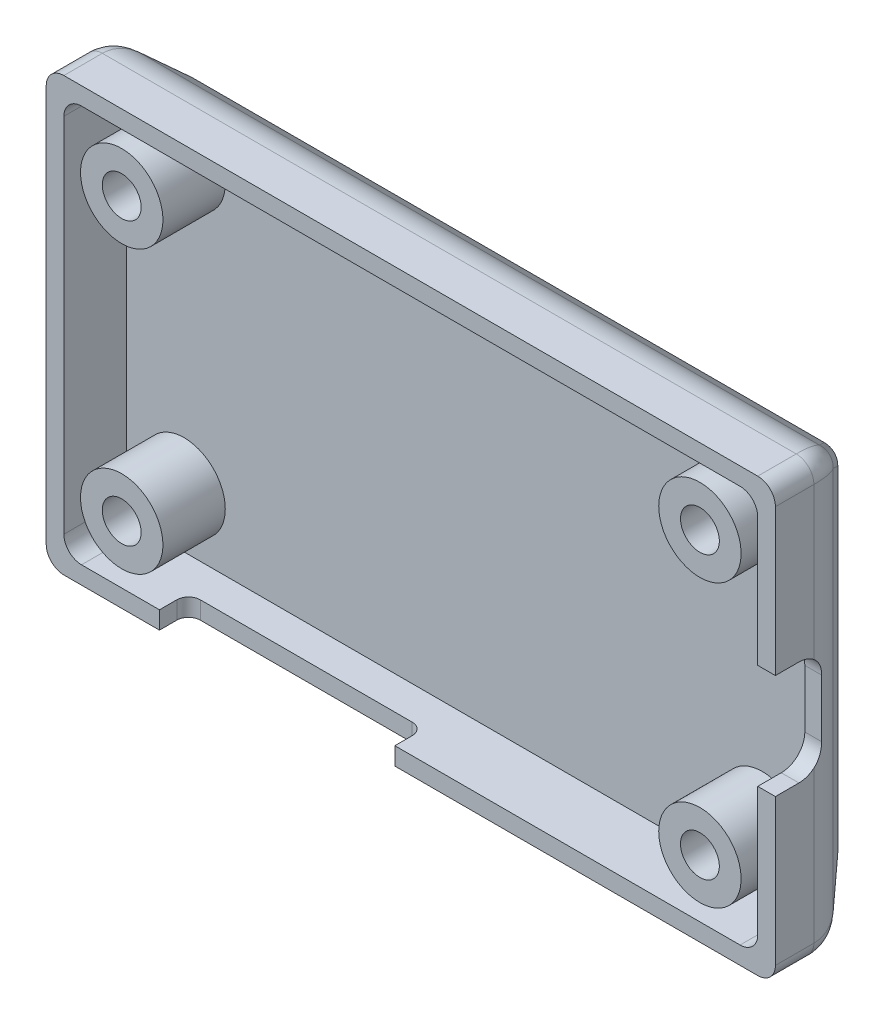
SolidWorks part; units mm, degrees
ref_plane "Alzado" through (0, 0, 0) normal (0, 0, 1) x (1, 0, 0)
ref_plane "Planta" through (0, 0, 0) normal (0, 1, 0) x (1, 0, 0)
ref_plane "Vista lateral" through (0, 0, 0) normal (1, 0, 0) x (0, 0, -1)
sketch "Croquis1" plane through (0, 0, 0) normal (0, 0, 1) x (1, 0, 0)
  line L1 (-21.6, 9) -> (21.6, 9) construction
  line L2 (-21.6, 9) -> (-21.6, -9) construction
  line L3 (-21.6, -9) -> (21.6, -9) construction
  line L4 (21.6, 9) -> (21.6, -9) construction
  line L5 (-21.6, 9) -> (21.6, -9) construction
  line L6 (-21.6, -9) -> (21.6, 9) construction
  line L7 (-22.6, 10) -> (22.6, 10) construction
  line L8 (-22.6, 10) -> (-22.6, -10) construction
  line L9 (-22.6, -10) -> (22.6, -10) construction
  line L10 (22.6, 10) -> (22.6, -10) construction
  line L11 (-22.6, 10) -> (22.6, -10) construction
  line L12 (-22.6, -10) -> (22.6, 10) construction
  line L18 (-27.974, 15.374) -> (-27.974, -15.374)
  line L20 (-27.974, -15.374) -> (27.974, -15.374)
  line L22 (27.974, -15.374) -> (27.974, 15.374)
  line L24 (27.974, 15.374) -> (-27.974, 15.374)
  line L25 (-30.975, -18.375) -> (30.975, -18.375)
  line L26 (-30.975, 18.375) -> (30.975, 18.375)
  line L27 (-30.975, 18.375) -> (-30.975, -18.375)
  line L29 (30.975, 18.375) -> (30.975, -18.375)
  line L30 (-30.975, 18.375) -> (30.975, -18.375) construction
  line L31 (-30.975, -18.375) -> (30.975, 18.375) construction
  circle A0 centre (-24.5622, 11.9622) radius 2.775
  circle A1 centre (-24.4031, -11.8031) radius 2.775
  circle A3 centre (24.5622, 11.9622) radius 2.775
  circle A4 centre (24.5622, -11.9622) radius 2.775
  point P0 (0, 0)
  point P6 (0, 0)
  point P19 (0, 0)
  dimension "D5" = 5.55
  dimension "D6" = 49.1244
  dimension "D1" = 43.2
  dimension "D2" = 18
  dimension "D3" = 45.2
  dimension "D4" = 20
  dimension "D7" = 61.95
  dimension "D8" = 36.75
  dimension "D9" = 23.7653
extrude "Saliente-Extruir1" add sketch "Croquis1" along normal blind 8.3 contours L27 L25 L29 L26 | A0 | A1 | A4 | A3
sketch "Croquis2" plane through (0, 0, 8.3) normal (0, 0, 1) x (1, 0, 0)
  line L0 (-46.0055, -20.2772) -> (-46.0055, -51.0253)
  line L1 (-46.0055, -51.0253) -> (9.9426, -51.0253)
  line L2 (9.9426, -51.0253) -> (9.9426, -20.2772)
  line L3 (9.9426, -20.2772) -> (-46.0055, -20.2772)
  line L5 (-29.475, 16.875) -> (29.475, 16.875)
  line L6 (-29.475, 16.875) -> (-29.475, -16.875)
  line L7 (-29.475, -16.875) -> (29.475, -16.875)
  line L8 (29.475, 16.875) -> (29.475, -16.875)
  line L9 (-29.475, 16.875) -> (29.475, -16.875) construction
  line L10 (-29.475, -16.875) -> (29.475, 16.875) construction
  point P4 (0, 0)
  dimension "D1" = 55.948
  dimension "D2" = 30.748
  dimension "D3" = 58.95
  dimension "D4" = 33.75
extrude "Cortar-Extruir1" cut sketch "Croquis2" against normal blind 5.3
chamfer "Chaflán4" distance 3 angle 50 4 edges at (-30.975, 0, 0) (0, -18.375, 0) (30.975, 0, 0) (0, 18.375, 0) first distance on face at (27.3372, -11.9622, 0)
fillet "Redondeo6" radius 4 4 edges at (0, 18.375, 3.5753) (-30.975, 0, 3.5753) (0, -18.375, 3.5753) (30.975, 0, 3.5753)
fillet "Redondeo7" radius 1.5 16 edges at (-30.975, -18.375, 6.6656) (-30.7338, -18.1338, 3.6631) (-29.0071, -16.4071, 1.23) (29.0071, 16.4071, 1.23) (30.7338, 18.1338, 3.6631) (29.0071, -16.4071, 1.23) (30.7338, -18.1338, 3.6631) (-29.0071, 16.4071, 1.23) (-30.7338, 18.1338, 3.6631) (30.975, 18.375, 6.6656) (30.975, -18.375, 6.6656) (-30.975, 18.375, 6.6656) (29.475, -16.875, 5.65) (29.475, 16.875, 5.65) (-29.475, 16.875, 5.65) (-29.475, -16.875, 5.65)
sketch "Croquis3" plane through (0, 0, 3) normal (0, 0, 1) x (1, 0, 0)
  line L1 (-29.826, 17.2183) -> (29.826, 17.2183)
  line L2 (-29.826, 17.2183) -> (-29.826, -17.2183)
  line L3 (-29.826, -17.2183) -> (29.826, -17.2183)
  line L4 (29.826, 17.2183) -> (29.826, -17.2183)
  line L5 (-29.826, 17.2183) -> (29.826, -17.2183) construction
  line L6 (-29.826, -17.2183) -> (29.826, 17.2183) construction
  point P0 (0, 0)
sketch "Croquis4" plane through (0, 0, 3) normal (0, 0, 1) x (1, 0, 0)
  circle A0 centre (-24.5622, 11.9622) radius 3.5
  circle A1 centre (-24.5622, 11.9622) radius 1.65
extrude "Saliente-Extruir2" add sketch "Croquis4" along normal up to surface (5.3 mm away) up to face at (0, 0, 8.3)
mirror "Simetría1" about plane through (0, 0, 0) normal (1, 0, 0) of "Saliente-Extruir2" second plane through (0, 0, 0) second plane normal (0, 1, 0)
sketch "Croquis5" plane through (30.975, 0, 0) normal (1, 0, 0) x (0, 0, -1)
  line L4 (-8.3, 16.875) -> (-8.3, -16.875) construction
  line L8 (-8.3, 4.45) -> (-8.3, -4.45)
  line L9 (-4.3, 4.45) -> (-4.3, -4.45)
  line L11 (-8.3, 4.45) -> (-4.3, 4.45)
  line L13 (-4.3, -4.45) -> (-8.3, -4.45)
  dimension "D3" = 8.9
extrude "Cortar-Extruir2" cut sketch "Croquis5" against normal blind 8
fillet "Redondeo8" radius 2 2 edges at (30.1913, -4.45, 4.3) (30.1913, 4.45, 4.3)
sketch "Croquis6" plane through (0, -18.375, 0) normal (0, -1, 0) x (-1, 0, 0)
  line L0 (21.355, -8.3) -> (1.355, -8.3)
  line L1 (29.475, -8.3) -> (-29.475, -8.3) construction
  line L2 (21.355, -8.3) -> (21.355, -5.8293)
  line L3 (21.355, -5.8293) -> (1.355, -5.8293)
  line L4 (1.355, -5.8293) -> (1.355, -8.3)
extrude "Cortar-Extruir3" cut sketch "Croquis6" against normal up to surface (1.5 mm away) up to face at (0, -16.875, 5.65)
fillet "Redondeo11" radius 1 2 edges at (-1.355, -17.625, 5.8293) (-21.355, -17.625, 5.8293)
